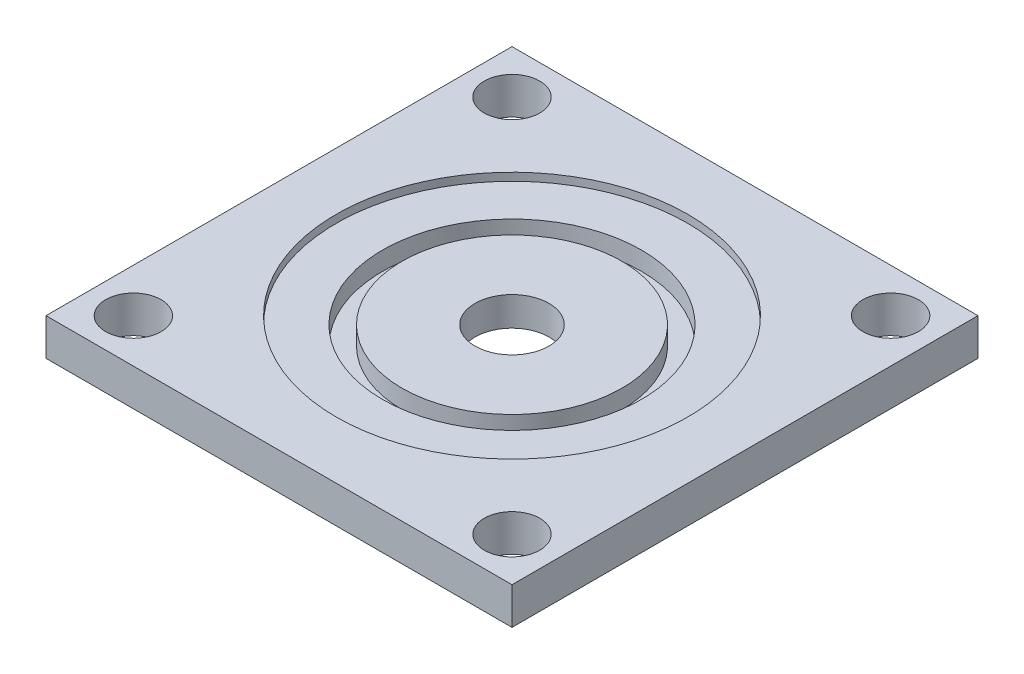
SolidWorks part; units mm, degrees
ref_plane "Front Plane" through (0, 0, 0) normal (0, 0, 1) x (1, 0, 0)
ref_plane "Top Plane" through (0, 0, 0) normal (0, 1, 0) x (1, 0, 0)
ref_plane "Right Plane" through (0, 0, 0) normal (1, 0, 0) x (0, 0, -1)
sketch "plateOutline" plane through (0, 0, 0) normal (0, 1, 0) x (1, 0, 0)
  line L1 (-40, -40) -> (40, -40)
  line L2 (-40, -40) -> (-40, 40)
  line L3 (-40, 40) -> (40, 40)
  line L4 (40, -40) -> (40, 40)
  line L5 (-40, -40) -> (40, 40) construction
  line L6 (-40, 40) -> (40, -40) construction
  line L7 (-40, -40) -> (40, -40) construction
  line L8 (-40, -40) -> (-40, 40) construction
  line L9 (-40, 40) -> (40, 40) construction
  line L10 (40, -40) -> (40, 40) construction
  point P0 (0, 0)
  dimension "D1" = 80
sketch "railGuides" plane through (0, 0, 0) normal (0, 1, 0) x (1, 0, 0)
  line L1 (-32.5, -32.5) -> (32.5, -32.5) construction
  line L2 (-32.5, -32.5) -> (-32.5, 32.5) construction
  line L3 (-32.5, 32.5) -> (32.5, 32.5) construction
  line L4 (32.5, -32.5) -> (32.5, 32.5) construction
  line L6 (-40, 40) -> (-25, 25) construction
  line L7 (40, 40) -> (25, 25) construction
  line L8 (25, -25) -> (40, -40) construction
  line L9 (-40, -40) -> (-25, -25) construction
  line L10 (-40, 40) -> (-25, 25) construction
  circle A0 centre (-32.5, 32.5) radius 4.7625
  circle A1 centre (32.5, 32.5) radius 4.7625
  circle A2 centre (32.5, -32.5) radius 4.7625
  circle A3 centre (-32.5, -32.5) radius 4.7625
sketch "FuelGrainMounting" plane through (0, 0, 0) normal (0, 1, 0) x (1, 0, 0)
  circle A0 centre (0, 0) radius 30.1625
sketch "GasIntake" plane through (0, 0, 0) normal (0, 1, 0) x (1, 0, 0)
  line L0 (-40, 40) -> (40, -40) construction
  circle A0 centre (0, 0) radius 6.35
extrude "Boss-Extrude1" add sketch "plateOutline" along normal blind 6.35 contours L3 L4 L1 L2
extrude "Cut-Extrude1" cut sketch "railGuides" along normal blind 10
extrude "Cut-Extrude2" cut sketch "FuelGrainMounting" along normal blind 5 from offset 5
extrude "Cut-Extrude3" cut sketch "GasIntake" along normal blind 5
sketch "Sketch1" plane through (0, 0, 0) normal (0, 1, 0) x (1, 0, 0)
  circle A0 centre (0, 0) radius 18.8787
  circle A2 centre (0, 0) radius 22.225
extrude "Cut-Extrude4" cut sketch "Sketch1" against normal blind 3.175 from offset 5
